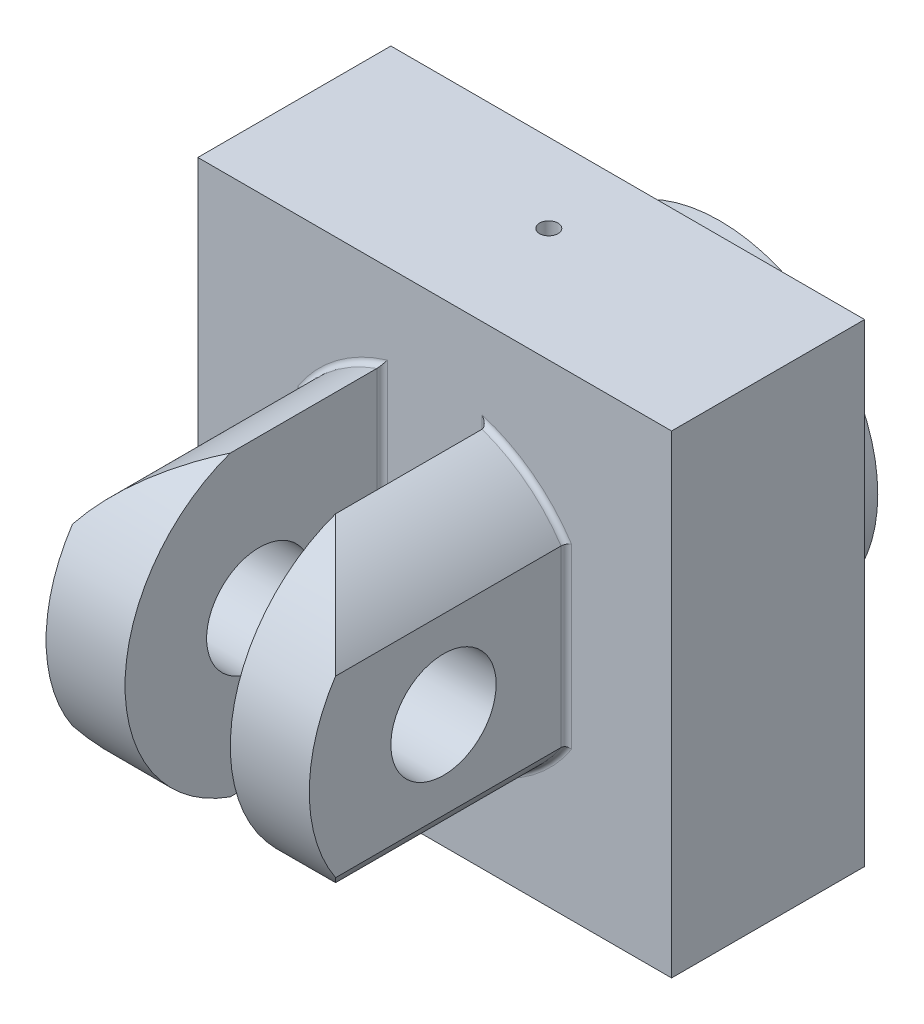
SolidWorks part; units mm, degrees
ref_plane "Front Plane" through (0, 0, 0) normal (0, 0, 1) x (1, 0, 0)
ref_plane "Top Plane" through (0, 0, 0) normal (0, 1, 0) x (1, 0, 0)
ref_plane "Right Plane" through (0, 0, 0) normal (1, 0, 0) x (0, 0, -1)
ref_plane "Otsapinta" through (0, 0, 17.5) normal (0, 0, 1) x (1, 0, 0)
ref_plane "77,5" through (0, 0, 77.5) normal (0, 0, 1) x (1, 0, 0)
ref_axis "Axis1" through (88.99, 0, 77.5) along (-1, 0, 0)
sketch "Sketch2" plane through (0, 0, 0) normal (0, 0, 1) x (1, 0, 0)
  line L1 (-45, 45) -> (45, 45)
  line L2 (-45, 45) -> (-45, -45)
  line L3 (-45, -45) -> (45, -45)
  line L4 (45, 45) -> (45, -45)
  point P4 (0, 45)
  point P7 (45, 0)
  dimension "D1" = 90
  dimension "D2" = 90
extrude "Boss-Extrude1" add sketch "Sketch2" along normal blind 103
sketch "Sketch3" plane through (0, 0, 0) normal (0, 1, 0) x (1, 0, 0)
  line L0 (0, 0) -> (0, -108.3396) construction
  point P3 (0, 0)
sketch "Sketch4" plane through (0, 0, 0) normal (0, 1, 0) x (1, 0, 0)
  line L0 (0, 0) -> (30, 0)
  line L1 (-49.5, 0) -> (49.5, 0) construction
  line L2 (30, 0) -> (30, -2.5)
  line L3 (30, 0) -> (70, 0)
  line L4 (30, 0) -> (30, -17.5)
  line L5 (30, -17.5) -> (70, -17.5)
  line L6 (70, 0) -> (70, -17.5)
  line L7 (0, -25) -> (0, -39.4207)
  line L8 (30, -2.5) -> (27, -2.5)
  line L9 (30, -2.5) -> (30, -6.5)
  line L10 (30, -6.5) -> (27, -6.5)
  line L11 (27, -2.5) -> (27, -6.5)
  line L12 (0, 0) -> (24, 0)
  line L13 (0, 0) -> (0, -25)
  line L14 (0, -25) -> (24, -25)
  line L15 (24, 0) -> (24, -25)
  line L16 (0, 0) -> (0, -108.3396) construction
  line L17 (0, -39.4207) -> (24, -25)
  dimension "D1" = 30
  dimension "D2" = 40
  dimension "D3" = 17.5
  dimension "D4" = 4
  dimension "D5" = 3
  dimension "D6" = 24
  dimension "D7" = 25
  dimension "D8" = 31
revolve "Cut-Revolve2" cut sketch "Sketch4" angle 360 about L0 region at (12, 0, 12.5) region at (8, 0, 29.8069)
sketch "Sketch5" plane through (0, 0, 0) normal (1, 0, 0) x (0, 0, -1)
  circle A0 centre (-77.5, 0) radius 10
extrude "Cut-Extrude1" cut sketch "Sketch5" against normal through all both and the other way through all
sketch "Sketch6" plane through (0, 0, 0) normal (1, 0, 0) x (0, 0, -1)
  line L0 (-103, 0) -> (-79.6698, 0)
  line L1 (-103, -45) -> (-103, 45) construction
  line L2 (0, 0) -> (-108.3396, 0) construction
  line L3 (-79.6698, 0) -> (-54.1698, 0)
  line L4 (-103, 0) -> (-73, 0)
  line L5 (-54.1698, 0) -> (-54.1698, 30)
  line L7 (-54.1698, 30) -> (-134.6694, 30)
  line L8 (-54.1698, 30) -> (-54.1698, 73.1012)
  line L9 (-54.1698, 73.1012) -> (-134.6694, 73.1012)
  line L10 (-134.6694, 30) -> (-134.6694, 73.1012)
revolve "Cut-Revolve3" cut sketch "Sketch6" angle 360 about L0 region at (0, 51.5506, 94.4196)
sketch "Sketch7" plane through (0, 0, 0) normal (1, 0, 0) x (0, 0, -1)
  line L0 (-103, 0) -> (-73, 0)
  line L1 (-103, 30) -> (-103, -30) construction
  line L2 (0, 0) -> (-108.3396, 0) construction
  line L3 (-77.5, 49.5) -> (-77.5, -49.5) construction
  line L4 (-103, 30) -> (-77.5, 30)
  line L5 (-103, 30) -> (-103, -30)
  line L6 (-103, -30) -> (-77.5, -30)
  line L7 (-77.5, 30) -> (-77.5, -30)
  line L8 (-103, -30) -> (-54.1698, -30) construction
  circle A0 centre (-73, 0) radius 30
extrude "Cut-Extrude2" cut sketch "Sketch7" against normal through all both and the other way through all contours A0 L7 L4 L5 | A0 L5 L6 L7 region at (0, -23.2816, 96.3515) region at (0, 23.2816, 96.3515)
sketch "Sketch8" plane through (0, 0, 54.1698) normal (0, 0, 1) x (1, 0, 0)
  line L1 (-10, 35) -> (10, 35)
  line L2 (-10, 35) -> (-10, -35)
  line L3 (-10, -35) -> (10, -35)
  line L4 (10, 35) -> (10, -35)
  line L5 (-25, 35) -> (25, 35)
  line L6 (-25, 35) -> (-25, -35)
  line L7 (-25, -35) -> (25, -35)
  line L8 (25, 35) -> (25, -35)
  circle A0 centre (0, 0) radius 30
  point P7 (10, 0)
  point P8 (0, -35)
  point P13 (25, 0)
  point P14 (0, 35)
  circle M9 centre (0, 0) radius 30
  dimension "D1" = 20
  dimension "D2" = 70
  dimension "D3" = 50
  dimension "D4" = 70
extrude "Cut-Extrude3" cut sketch "Sketch8" along normal blind 103 contours L8 M9 | L6 M9 | L4 L2 M9 region at (0, 0, 54.1698) region at (-27.015, 0, 54.1698) region at (27.015, 0, 54.1698)
sketch "Sketch10" plane through (0, 45, 0) normal (0, 1, 0) x (1, 0, 0)
  line L0 (0, -17.5) -> (0, -32.5)
  line L2 (0, 0) -> (0, -108.3396) construction
  line L3 (-49.5, -17.5) -> (49.5, -17.5) construction
  circle A0 centre (0, -32.5) radius 1.75
  point P9 (0, -33.0006)
  dimension "D1" = 3.5
extrude "Cut-Extrude4" cut sketch "Sketch10" against normal up to next contours A0
fillet "Fillet1" radius 1 9 edges at (-10, 0, 54.1698) (-18.4521, 23.6542, 54.1698) (-25, 0, 54.1698) (-18.4521, -23.6542, 54.1698) (10, 0, 54.1698) (18.4521, -23.6542, 54.1698) (25, 0, 54.1698) (18.4521, 23.6542, 54.1698) (-30, 0, 17.5)
sketch "Sketch14" plane through (0, 0, 17.5) normal (0, 0, -1) x (-1, 0, 0)
  line L0 (0, 0) -> (-45, 45)
  circle A0 centre (0, 0) radius 45
sketch "Sketch17" plane through (0, 45, 0) normal (0, 1, 0) x (1, 0, 0)
  line L0 (0, -17.5) -> (0, -32.5)
  line L1 (45, -17.5) -> (-45, -17.5) construction
  line L2 (0, 0) -> (0, -108.3396) construction
  dimension "D1" = 15
